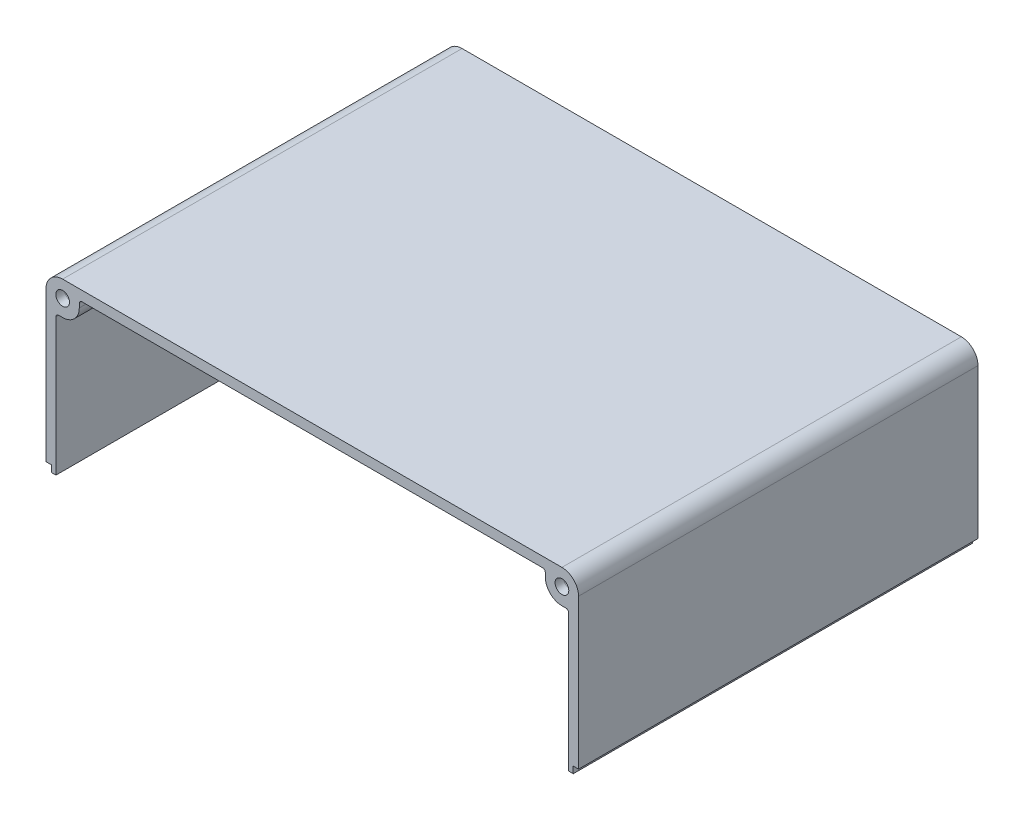
SolidWorks part; units mm, degrees
ref_plane "Front Plane" through (0, 0, 0) normal (0, 0, 1) x (1, 0, 0)
ref_plane "Top Plane" through (0, 0, 0) normal (0, 1, 0) x (1, 0, 0)
ref_plane "Right Plane" through (0, 0, 0) normal (1, 0, 0) x (0, 0, -1)
sketch "Sketch1" plane through (0, 0, 0) normal (0, 0, 1) x (1, 0, 0)
  line L1 (-101.6, -33.02) -> (101.6, -33.02)
  line L2 (-101.6, -33.02) -> (-101.6, 33.02)
  line L3 (-101.6, 33.02) -> (101.6, 33.02)
  line L4 (101.6, -33.02) -> (101.6, 33.02)
  line L5 (-101.6, -33.02) -> (101.6, 33.02) construction
  line L6 (-101.6, 33.02) -> (101.6, -33.02) construction
  point P0 (0, 0)
  dimension "D1" = 203.2
  dimension "D2" = 66.04
extrude "Boss-Extrude1" add sketch "Sketch1" against normal mid plane 152.4
fillet "Fillet1" radius 6.35 2 edges at (101.6, 33.02, 0) (-101.6, 33.02, 0)
sketch "Sketch2" plane through (0, 0, 76.2) normal (0, 0, 1) x (1, 0, 0)
  line L3 (-97.79, -33.02) -> (97.79, -33.02)
  line L6 (97.79, -33.02) -> (97.79, 26.67)
  line L7 (95.25, 29.21) -> (-95.25, 29.21)
  line L8 (-97.79, 26.67) -> (-97.79, -33.02)
  line L9 (97.79, -33.02) -> (97.79, 26.67)
  line L10 (95.25, 29.21) -> (-95.25, 29.21)
  line L11 (-97.79, 26.67) -> (-97.79, -33.02)
  arc A4 (97.79, 26.67) -> (95.25, 29.21) centre (95.25, 26.67) ccw
  arc A5 (-95.25, 29.21) -> (-97.79, 26.67) centre (-95.25, 26.67) ccw
  arc A6 (97.79, 26.67) -> (95.25, 29.21) centre (95.25, 26.67) ccw
  arc A7 (-95.25, 29.21) -> (-97.79, 26.67) centre (-95.25, 26.67) ccw
  dimension "D1" = 3.81
extrude "Cut-Extrude1" cut sketch "Sketch2" against normal through all
sketch "Sketch3" plane through (0, 0, 76.2) normal (0, 0, 1) x (1, 0, 0)
  line L0 (0, 0) -> (0, -25.5874) construction
  line L1 (99.568, -33.02) -> (99.568, -30.48)
  line L2 (-101.6, -33.02) -> (-99.568, -33.02)
  line L3 (-101.6, -33.02) -> (-101.6, -30.48)
  line L4 (-101.6, -30.48) -> (-99.568, -30.48)
  line L5 (-99.568, -33.02) -> (-99.568, -30.48)
  line L6 (101.6, -30.48) -> (99.568, -30.48)
  line L7 (101.6, -33.02) -> (101.6, -30.48)
  line L8 (101.6, -33.02) -> (99.568, -33.02)
  dimension "D1" = 2.54
  dimension "D2" = 2.032
extrude "Cut-Extrude2" cut sketch "Sketch3" against normal through all
sketch "Sketch4" plane through (0, 0, 76.2) normal (0, 0, 1) x (1, 0, 0)
  line L0 (-95.25, 20.32) -> (-97.79, 20.32)
  line L1 (-97.79, 26.67) -> (-97.79, -33.02) construction
  line L2 (-88.9, 26.67) -> (-88.9, 29.21)
  line L3 (95.25, 29.21) -> (-95.25, 29.21) construction
  line L4 (-95.25, 29.21) -> (-88.9, 29.21)
  line L5 (-97.79, 26.67) -> (-97.79, 20.32)
  line L6 (0, 0) -> (0, 41.8572) construction
  line L7 (97.79, 26.67) -> (97.79, 20.32)
  line L8 (95.25, 29.21) -> (88.9, 29.21)
  line L9 (88.9, 26.67) -> (88.9, 29.21)
  line L10 (95.25, 20.32) -> (97.79, 20.32)
  arc A0 (-95.25, 20.32) -> (-88.9, 26.67) centre (-95.25, 26.67) ccw
  arc A1 (-95.25, 29.21) -> (-97.79, 26.67) centre (-95.25, 26.67) ccw construction
  arc A2 (-95.25, 29.21) -> (-97.79, 26.67) centre (-95.25, 26.67) ccw
  arc A3 (95.25, 29.21) -> (97.79, 26.67) centre (95.25, 26.67) cw
  arc A4 (95.25, 20.32) -> (88.9, 26.67) centre (95.25, 26.67) cw
  dimension "D1" = 12.7
  dimension "D2" = 190.5
extrude "Boss-Extrude3" add sketch "Sketch4" against normal blind 19.05
mirror "Mirror1" about plane through (0, 0, 0) normal (0, 0, 1) of "Boss-Extrude3"
draft "Draft1" type of draft neutral plane draft angle 45 faces to draft 4 face at (-93.8485, 25.2685, 57.15) face at (93.8485, 25.2685, -57.15) face at (93.8485, 25.2685, 57.15) face at (-93.8485, 25.2685, -57.15) neutral plane through (95.25, 29.21, -76.2) neutral plane normal (0, -1, 0) parameters "D1"=45
hole_wizard "CSK for #8 Flat Head Machine Screw (100)1" positions "Sketch5" profile "Sketch7" countersink size "#8" standard "ANSI Inch"
sketch "Sketch5" plane through (0, 0, 76.2) normal (0, 0, 1) x (1, 0, 0)
  point P0 (-95.25, 26.67)
  point P3 (95.25, 26.67)
sketch "Sketch7" plane through (-95.25, 26.67, 76.2) normal (1, 0, 0) x (0, -1, 0)
  line L0 (0, 0) -> (0, 7.7617)
  line L1 (0, 7.7617) -> (2.3495, 6.35)
  line L2 (2.3495, 6.35) -> (2.3495, 3.0484)
  line L3 (2.3495, 3.0484) -> (2.6162, 0)
  line L5 (2.6162, 0) -> (0, 0)
  line L6 (-2.3495, 3.0484) -> (-2.6162, 0) construction
  line L10 (0, 7.7617) -> (-2.3495, 6.35) construction
  line L11 (0, -6.35) -> (0, 107.95) construction
  dimension "Hole Dia." = 4.699
  dimension "Hole Depth" = 6.35
  dimension "Near C'Sink Dia." = 5.2324
  dimension "Near C'Sink Angle" = 10
  dimension "Drill Angle" = 118
hole_wizard "CSK for #8 Flat Head Machine Screw (100)2" positions "Sketch8" profile "Sketch9" countersink size "#8" standard "ANSI Inch"
sketch "Sketch8" plane through (0, 0, -76.2) normal (0, 0, -1) x (-1, 0, 0)
  point P0 (-95.25, 26.67)
  point P3 (95.25, 26.67)
sketch "Sketch9" plane through (95.25, 26.67, -76.2) normal (1, 0, 0) x (0, 1, 0)
  line L0 (0, 0) -> (0, 7.7617)
  line L1 (0, 7.7617) -> (2.3495, 6.35)
  line L2 (2.3495, 6.35) -> (2.3495, 3.0484)
  line L3 (2.3495, 3.0484) -> (2.6162, 0)
  line L5 (2.6162, 0) -> (0, 0)
  line L6 (-2.3495, 3.0484) -> (-2.6162, 0) construction
  line L10 (0, 7.7617) -> (-2.3495, 6.35) construction
  line L11 (0, -6.35) -> (0, 107.95) construction
  dimension "Hole Dia." = 4.699
  dimension "Hole Depth" = 6.35
  dimension "Near C'Sink Dia." = 5.2324
  dimension "Near C'Sink Angle" = 10
  dimension "Drill Angle" = 118
fillet "Fillet2" radius 1.016 32 edges at (88.9, 29.21, 66.675) (97.79, 20.32, 71.12) (88.9, 29.21, -66.675) (97.79, 20.32, -71.12) (-97.79, 20.32, -71.12) (-88.9, 29.21, -66.675) (-88.9, 29.21, 66.675) (-97.79, 20.32, 71.12) (-97.79, 23.495, 62.865) (-97.0461, 28.4661, 57.8939) (-92.075, 29.21, 57.15) (-88.9, 27.94, 58.42) (-96.52, 20.32, 66.04) (-90.7599, 22.1799, 64.1801) (97.79, 23.495, -62.865) (96.52, 20.32, -66.04) (90.7599, 22.1799, -64.1801) (88.9, 27.94, -58.42) (92.075, 29.21, -57.15) (97.0461, 28.4661, -57.8939) (-96.52, 20.32, -66.04) (-97.79, 23.495, -62.865) (-97.0461, 28.4661, -57.8939) (-92.075, 29.21, -57.15) (-88.9, 27.94, -58.42) (-90.7599, 22.1799, -64.1801) (92.075, 29.21, 57.15) (88.9, 27.94, 58.42) (90.7599, 22.1799, 64.1801) (96.52, 20.32, 66.04) (97.79, 23.495, 62.865) (97.0461, 28.4661, 57.8939)
